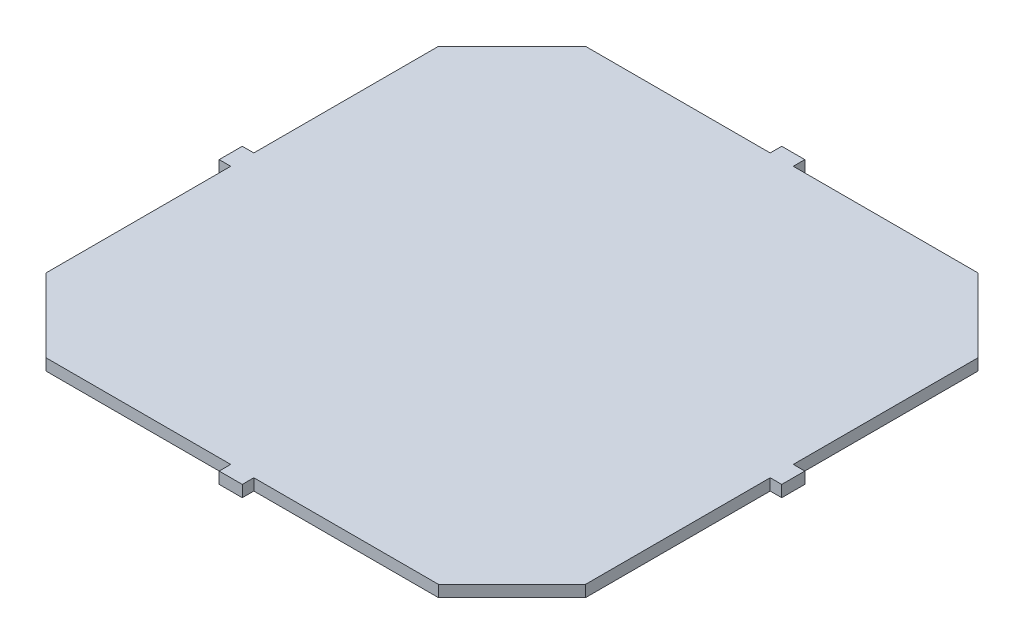
SolidWorks part; units mm, degrees
material "ABS PC"
ref_plane "Front Plane" through (0, 0, 0) normal (0, 0, 1) x (1, 0, 0)
ref_plane "Top Plane" through (0, 0, 0) normal (0, 1, 0) x (1, 0, 0)
ref_plane "Right Plane" through (0, 0, 0) normal (1, 0, 0) x (0, 0, -1)
sketch "Sketch1" plane through (0, 0, 0) normal (0, 1, 0) x (1, 0, 0)
  line L0 (-23.364, 17) -> (-17, 23.364)
  line L1 (-17, -23.364) -> (17, -23.364)
  line L2 (-23.364, -17) -> (-23.364, 17)
  line L3 (-17, 23.364) -> (17, 23.364)
  line L4 (23.364, -17) -> (23.364, 17)
  line L5 (-20.182, -20.182) -> (20.182, 20.182) construction
  line L6 (-20.182, 20.182) -> (20.182, -20.182) construction
  line L7 (-23.364, -17) -> (-17, -23.364)
  line L8 (17, -23.364) -> (23.364, -17)
  line L9 (17, 23.364) -> (23.364, 17)
  point P0 (0, 0)
  dimension "D1" = 34
  dimension "D2" = 34
  dimension "D3" = 135
  dimension "D4" = 135
  dimension "D5" = 9
  dimension "D6" = 135
extrude "Boss-Extrude1" add sketch "Sketch1" along normal blind 1
sketch "Sketch2" plane through (0, 1, 0) normal (0, 1, 0) x (1, 0, 0)
  line L0 (0, 23.364) -> (0, -23.364) construction
  line L1 (17, 23.364) -> (-17, 23.364) construction
  line L2 (-17, -23.364) -> (17, -23.364) construction
  line L3 (-23.364, 0) -> (23.364, 0) construction
  line L4 (-23.364, 17) -> (-23.364, -17) construction
  line L5 (23.364, -17) -> (23.364, 17) construction
  line L6 (-23.364, 1) -> (-24.364, 1)
  line L7 (-24.364, 1) -> (-24.364, -1)
  line L8 (-24.364, -1) -> (-23.364, -1)
  line L9 (-1, 23.364) -> (-1, 24.364)
  line L10 (-1, 24.364) -> (1, 24.364)
  line L11 (1, 24.364) -> (1, 23.364)
  line L12 (1, -24.364) -> (1, -23.364)
  line L13 (-1, -24.364) -> (1, -24.364)
  line L14 (-1, -23.364) -> (-1, -24.364)
  line L15 (24.364, -1) -> (23.364, -1)
  line L16 (24.364, 1) -> (24.364, -1)
  line L17 (23.364, 1) -> (24.364, 1)
  line L18 (-1, 23.364) -> (1, 23.364)
  line L19 (23.364, 1) -> (23.364, -1)
  line L20 (-1, -23.364) -> (1, -23.364)
  line L21 (-23.364, -1) -> (-23.364, 1)
  dimension "D1" = 2
  dimension "D2" = 1
  dimension "D3" = 2
  dimension "D4" = 1
extrude "Boss-Extrude2" add sketch "Sketch2" against normal blind 1
